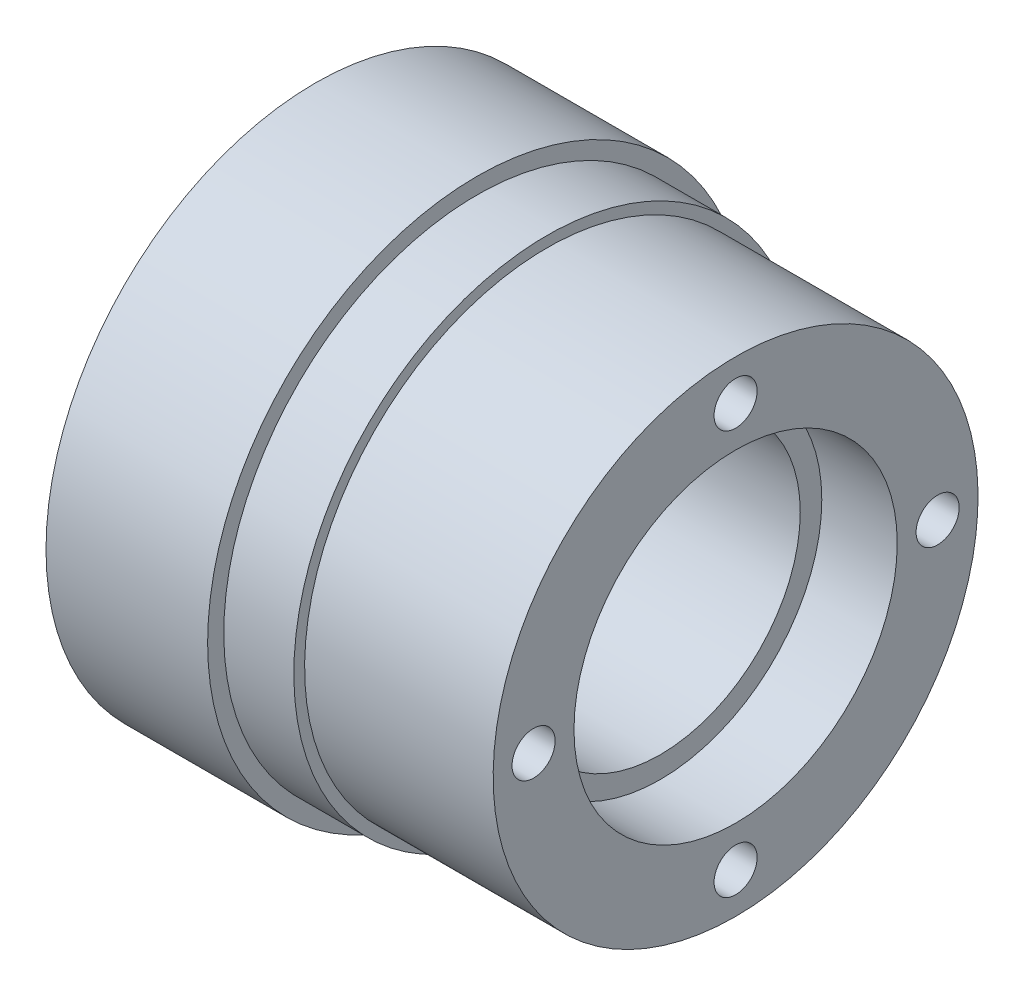
SolidWorks part; units mm, degrees
ref_plane "Front Plane" through (0, 0, 0) normal (0, 0, 1) x (1, 0, 0)
ref_plane "Top Plane" through (0, 0, 0) normal (0, 1, 0) x (1, 0, 0)
ref_plane "Right Plane" through (0, 0, 0) normal (1, 0, 0) x (0, 0, -1)
sketch "Sketch1" plane through (0, 0, 0) normal (0, 0, 1) x (1, 0, 0)
  line L0 (-19.5, 0) -> (19.5, 0) construction
  line L1 (-19.5, 13.5) -> (-15.3, 13.5)
  line L2 (-15.3, 13.5) -> (-15.3, 13)
  line L3 (-15.3, 13) -> (12.5, 13)
  line L4 (12.5, 13) -> (12.5, 15)
  line L5 (12.5, 15) -> (19.5, 15)
  line L6 (19.5, 15) -> (19.5, 22.5)
  line L7 (19.5, 22.5) -> (2, 22.5)
  line L8 (2, 22.5) -> (2, 23.5)
  line L9 (2, 23.5) -> (-4.5, 23.5)
  line L10 (-4.5, 23.5) -> (-4.5, 25)
  line L11 (-4.5, 25) -> (-19.5, 25)
  line L12 (-19.5, 25) -> (-19.5, 13.5)
  point P4 (0, 0)
  point P21 (2, 23)
  dimension "D1" = 39
  dimension "D2" = 7
  dimension "D3" = 26
  dimension "D4" = 27
  dimension "D5" = 30
  dimension "D6" = 4.2
  dimension "D7" = 50
  dimension "D8" = 45
  dimension "D9" = 47
  dimension "D10" = 15
  dimension "D11" = 17.5
revolve "Revolve1" add sketch "Sketch1" angle 360 about L0
sketch "Sketch2" plane through (19.5, 0, 0) normal (1, 0, 0) x (0, 0, -1)
  line L0 (0, 22.5) -> (0, 15) construction
  circle A0 centre (0, 18.75) radius 2
  circle A1 centre (0, 0) radius 22.5 construction
  circle A2 centre (0, 0) radius 22.5 construction
  circle A3 centre (0, 0) radius 15 construction
  circle A4 centre (18.75, 0) radius 2
  circle A5 centre (0, -18.75) radius 2
  circle A6 centre (-18.75, 0) radius 2
  point P21 (0, 0)
  dimension "D1" = 4
  dimension "D2" = 18.75
  dimension "D3" = 18.75
extrude "Cut-Extrude1" cut sketch "Sketch2" against normal blind 10
sketch "Sketch3" plane through (-19.5, 0, 0) normal (-1, 0, 0) x (0, 0, 1)
  line L0 (0, 13.5) -> (0, 25) construction
  circle A0 centre (0, 0) radius 13.5 construction
  circle A1 centre (0, 0) radius 13.5 construction
  circle A2 centre (0, 0) radius 25 construction
  circle A3 centre (0, 19.25) radius 2
  circle A4 centre (19.25, 0) radius 2
  circle A5 centre (0, -19.25) radius 2
  circle A6 centre (-19.25, 0) radius 2
  point P19 (0, 0)
  dimension "D1" = 4
  dimension "D2" = 19.25
  dimension "D3" = 19.25
extrude "Cut-Extrude2" cut sketch "Sketch3" against normal blind 10
